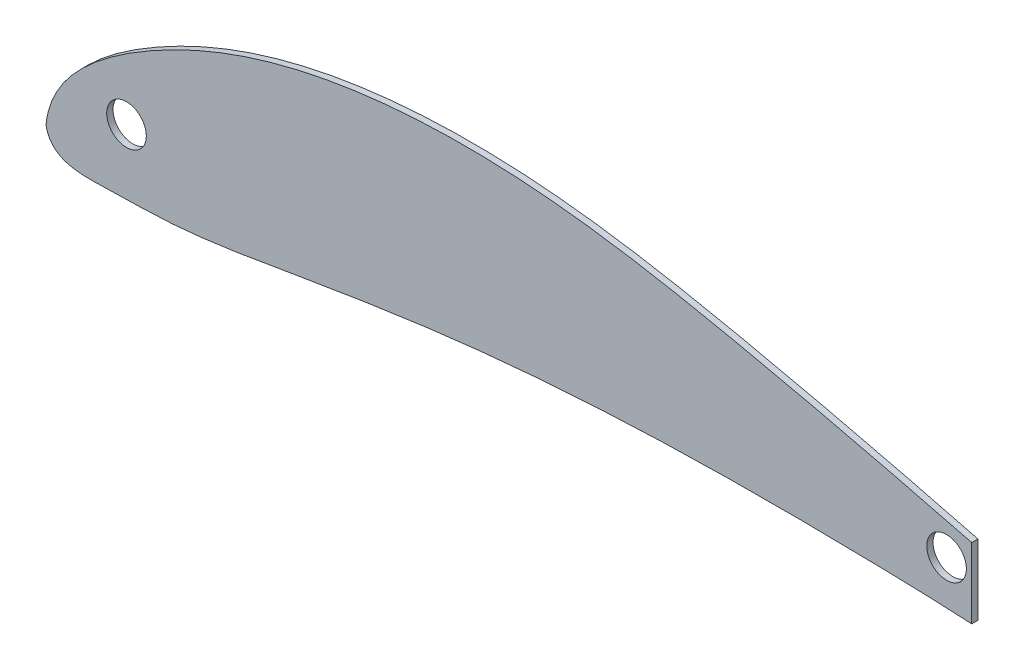
SolidWorks part; units mm, degrees
material "Balsa"
ref_plane "Front Plane" through (0, 0, 0) normal (0, 0, 1) x (1, 0, 0)
ref_plane "Top Plane" through (0, 0, 0) normal (0, 1, 0) x (1, 0, 0)
ref_plane "Right Plane" through (0, 0, 0) normal (1, 0, 0) x (0, 0, -1)
sketch "Sketch1" plane through (0, 0, 0) normal (0, 0, 1) x (1, 0, 0)
  spline S0 degree 3 poles (0.0006, 0.0001) (0.8106, 7.3592) (8.6491, 17.8566) (26.2867, 29.9752) (52.1111, 42.0692) (89.5976, 49.2908) (131.4008, 47.8848) (173.2567, 40.0411) (217.9611, 29.613) (256.9521, 19.5289) (290.3598, 8.711) (301.2732, 4.3828) (314.8169, -0.5162) (309.8463, 0.0001) knots 0 0 0 0 0.060864 0.113688 0.188609 0.312909 0.448482 0.557612 0.691544 0.852438 0.929756 0.976058 1 1 1 1
  spline S1 degree 3 poles (309.8463, 0.0001) (303.9568, 1.471) (293.9895, 2.094) (276.264, 4.5144) (260.8463, 5.4274) (235.8588, 7.8703) (205.1014, 8.8381) (157.7186, 9.0307) (110.4973, 6.1815) (66.5062, -0.5867) (36.4547, -6.0985) (15.3166, -6.1891) (1.2307, -6.9241) (0.0006, 0.0001) knots 0 0 0 0 0.057787 0.095275 0.171021 0.205339 0.335319 0.464904 0.658702 0.785512 0.893517 0.943092 1 1 1 1
extrude "Boss-Extrude1" add sketch "Sketch1" along normal blind 1.5875
sketch "Sketch2" plane through (0, 0, 1.5875) normal (0, 0, 1) x (1, 0, 0)
  circle A0 centre (20.32, 10.16) radius 5
  circle A1 centre (227.2963, 19.0501) radius 5
  dimension "D2" = 10
  dimension "D3" = 10
  dimension "D6" = 20.32
  dimension "D1" = 82.55
  dimension "D4" = 19.05
  dimension "D5" = 10.16
extrude "Cut-Extrude1" cut sketch "Sketch2" against normal through all
sketch "Sketch3" plane through (0, 0, 1.5875) normal (0, 0, 1) x (1, 0, 0)
  line L1 (350.4863, -6.3499) -> (233.6463, -6.3499)
  line L2 (350.4863, -6.3499) -> (350.4863, 44.4501)
  line L3 (350.4863, 44.4501) -> (233.6463, 44.4501)
  line L4 (233.6463, -6.3499) -> (233.6463, 44.4501)
  circle A0 centre (227.2963, 19.0501) radius 5 construction
  dimension "D1" = 6.35
  dimension "D2" = 116.84
  dimension "D3" = 50.8
  dimension "D4" = 44.45
extrude "Cut-Extrude2" cut sketch "Sketch3" against normal through all contours L3 L4 L1 L2
